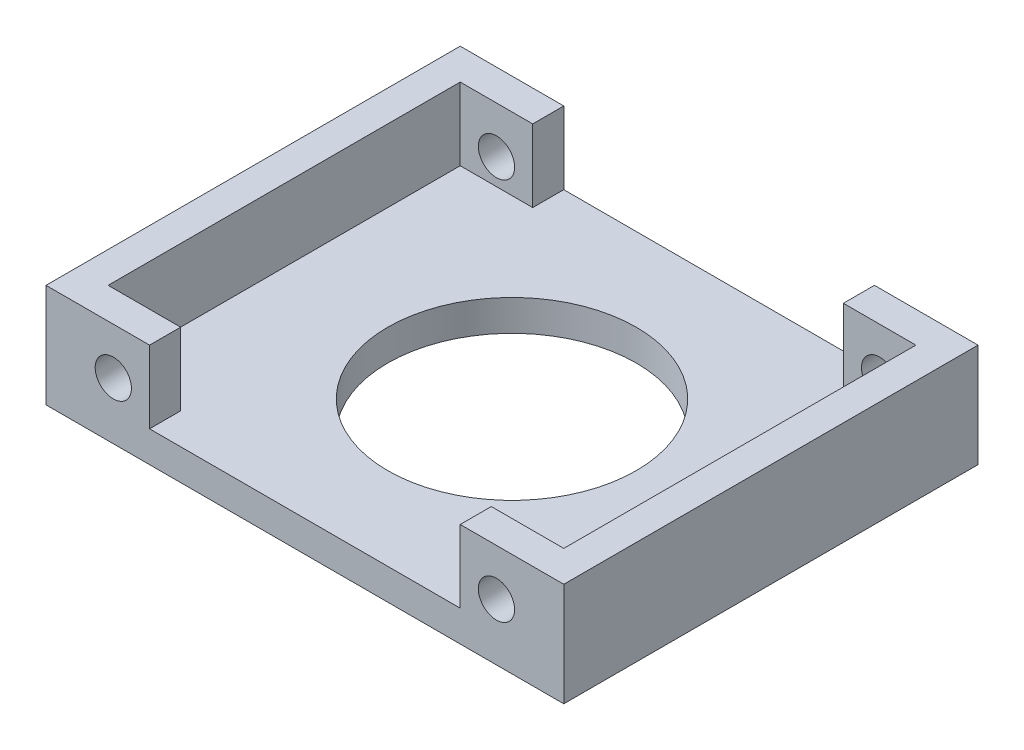
SolidWorks part; units mm, degrees
ref_plane "Front Plane" through (0, 0, 0) normal (0, 0, 1) x (1, 0, 0)
ref_plane "Top Plane" through (0, 0, 0) normal (0, 1, 0) x (1, 0, 0)
ref_plane "Right Plane" through (0, 0, 0) normal (1, 0, 0) x (0, 0, -1)
sketch "Sketch1" plane through (0, 0, 0) normal (0, 1, 0) x (1, 0, 0)
  line L1 (-25, 20) -> (25, 20)
  line L2 (-25, 20) -> (-25, -20)
  line L3 (-25, -20) -> (25, -20)
  line L4 (25, 20) -> (25, -20)
  line L5 (-25, 20) -> (25, -20) construction
  line L6 (-25, -20) -> (25, 20) construction
  point P0 (0, 0)
  dimension "D1" = 50
  dimension "D2" = 40
extrude "Boss-Extrude1" add sketch "Sketch1" along normal blind 3
sketch "Sketch2" plane through (0, 3, 0) normal (0, 1, 0) x (1, 0, 0)
  circle A0 centre (0, 0) radius 12
  dimension "D1" = 24
extrude "Cut-Extrude1" cut sketch "Sketch2" against normal through all
sketch "Sketch3" plane through (0, 3, 0) normal (0, 1, 0) x (1, 0, 0)
  line L0 (-25, -20) -> (25, -20) construction
  line L1 (-25, 20) -> (-22, 20)
  line L2 (-25, 20) -> (-25, -20)
  line L3 (-25, -20) -> (-22, -20)
  line L4 (-22, 20) -> (-22, -20)
  line L6 (22, -20) -> (25, -20)
  line L7 (22, -20) -> (22, 20)
  line L8 (22, 20) -> (25, 20)
  line L9 (25, -20) -> (25, 20)
  dimension "D1" = 3
extrude "Boss-Extrude2" add sketch "Sketch3" along normal blind 7
sketch "Sketch4" plane through (0, 0, 20) normal (0, 0, 1) x (1, 0, 0)
  line L1 (-22, 3) -> (-15, 3)
  line L2 (-22, 3) -> (-22, 10)
  line L3 (-22, 10) -> (-15, 10)
  line L4 (-15, 3) -> (-15, 10)
  line L5 (22, 3) -> (15, 3)
  line L6 (22, 3) -> (22, 10)
  line L7 (22, 10) -> (15, 10)
  line L8 (15, 3) -> (15, 10)
  dimension "D2" = 7
  dimension "6" = 7
extrude "Boss-Extrude3" add sketch "Sketch4" against normal blind 3
sketch "Sketch5" plane through (0, 0, 20) normal (0, 0, 1) x (1, 0, 0)
  line L0 (-18.5, 10) -> (-18.5, 5.5) construction
  line L2 (18.5, 10) -> (18.5, 5.5) construction
  line L3 (-25, 0) -> (25, 0) construction
  line L4 (-18.5, 5.5) -> (18.5, 5.5) construction
  line L6 (-22, 10) -> (-15, 10) construction
  line L7 (-25, 10) -> (-15, 10) construction
  line L8 (15, 10) -> (22, 10) construction
  line L9 (15, 10) -> (15, 3) construction
  line L10 (15, 10) -> (25, 10) construction
  circle A0 centre (-18.5, 5.5) radius 1.75
  circle A1 centre (18.5, 5.5) radius 1.75
  point P8 (15, 10)
  point P17 (0, 0)
  point P18 (0, 0)
  point P25 (0, 0)
  dimension "D1" = 3.5
  dimension "D2" = 3.5
  dimension "D3" = 5.5
extrude "Cut-Extrude2" cut sketch "Sketch5" against normal through all
mirror "Mirror1" about plane through (0, 0, 0) normal (0, 0, 1) of "Cut-Extrude2", "Boss-Extrude3"
